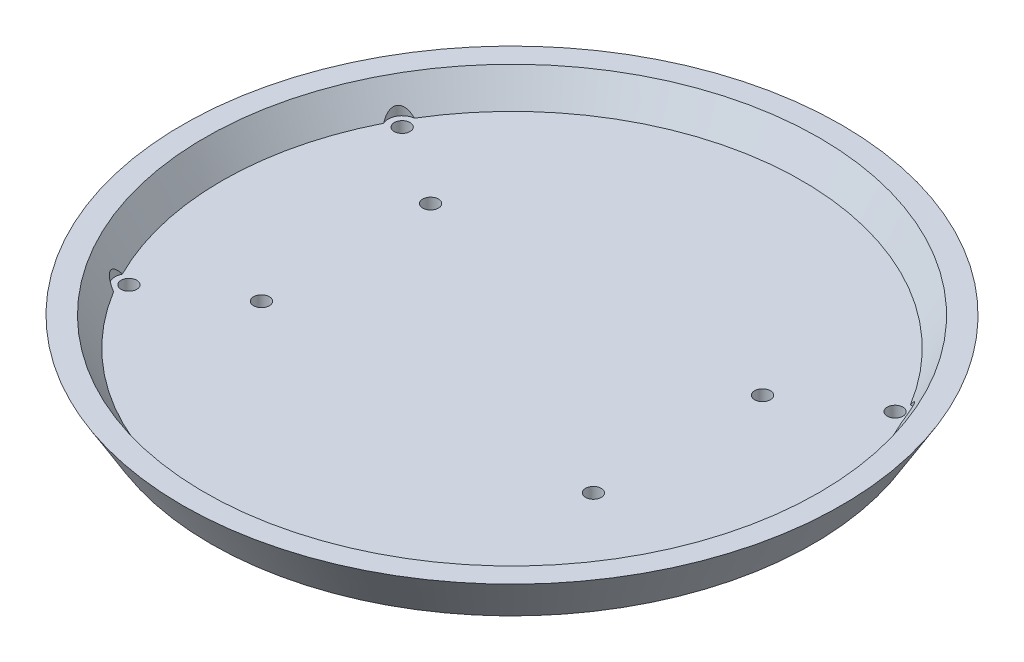
SolidWorks part; units mm, degrees
ref_plane "Front Plane" through (0, 0, 0) normal (0, 0, 1) x (1, 0, 0)
ref_plane "Top Plane" through (0, 0, 0) normal (0, 1, 0) x (1, 0, 0)
ref_plane "Right Plane" through (0, 0, 0) normal (1, 0, 0) x (0, 0, -1)
sketch "Sketch1" plane through (0, 0, 0) normal (0, 0, 1) x (1, 0, 0)
  line L0 (0, -4) -> (63, -4)
  line L1 (63, -4) -> (69, 6)
  line L6 (0, 0) -> (60.7352, 0)
  line L7 (60.7352, 0) -> (64.3352, 6)
  line L8 (69, 6) -> (64.3352, 6)
  line L9 (0, -4) -> (0, 0)
  line L10 (60.7352, 0) -> (65.57, 8.058) construction
  point P2 (1.2454, -6.3799)
  point P8 (0, 0)
  dimension "D1" = 69
  dimension "D2" = 63
  dimension "D3" = 10
  dimension "D4" = 4
revolve "Revolve1" add sketch "Sketch1" angle 360 about L9
sketch "Sketch4" plane through (0, 0, 0) normal (0, 1, 0) x (1, 0, 0)
  line L0 (-60.7352, 0) -> (60.7352, 0) construction
  line L1 (0, 60.7352) -> (0, -60.7352) construction
  line L2 (0, 0) -> (34.7493, 17.7056) construction
  line L3 (0, 0) -> (51.6026, 28.6038) construction
  circle A0 centre (0, 0) radius 60.7352 construction
  circle A1 centre (34.7493, 17.7056) radius 1.65
  circle A2 centre (51.6026, 28.6038) radius 1.65
  circle A4 centre (51.6026, -28.6038) radius 1.65
  circle A5 centre (34.7493, -17.7056) radius 1.65
  circle A6 centre (-34.7493, -17.7056) radius 1.65
  circle A7 centre (-51.6026, -28.6038) radius 1.65
  circle A8 centre (-51.6026, 28.6038) radius 1.65
  circle A9 centre (-34.7493, 17.7056) radius 1.65
  dimension "D5" = 3.3
  dimension "D6" = 3.3
  dimension "D1" = 27
  dimension "D2" = 29
  dimension "D3" = 39
  dimension "D4" = 59
extrude "Cut-Extrude1" cut sketch "Sketch4" against normal through all
sketch "Sketch5" plane through (0, 0, 0) normal (0, 1, 0) x (1, 0, 0)
  circle A0 centre (51.6026, 28.6038) radius 2.9
  circle A1 centre (51.6026, -28.6038) radius 2.9
  circle A2 centre (-51.6026, -28.6038) radius 2.9
  circle A3 centre (-51.6026, 28.6038) radius 2.9
  dimension "D1" = 5.8
extrude "Cut-Extrude2" cut sketch "Sketch5" along normal through all
